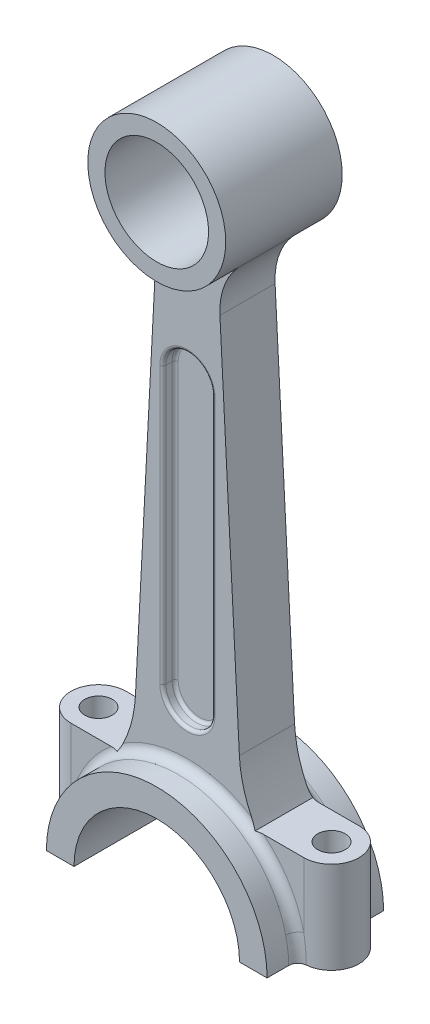
SolidWorks part; units mm, degrees
ref_plane "Front Plane" through (0, 0, 0) normal (0, 0, 1) x (1, 0, 0)
ref_plane "Top Plane" through (0, 0, 0) normal (0, 1, 0) x (1, 0, 0)
ref_plane "Right Plane" through (0, 0, 0) normal (1, 0, 0) x (0, 0, -1)
sketch "Sketch2" plane through (0, 0, 0) normal (0, 0, 1) x (1, 0, 0)
  line L0 (0, 0) -> (0, -201.2) construction
  line L1 (-10, -20.1556) -> (-17.8497, -169.9368)
  line L2 (10, -20.1556) -> (17.8497, -169.9368)
  line L3 (-36, -201.2) -> (-27, -201.2)
  line L4 (27, -201.2) -> (36, -201.2)
  circle A0 centre (0, 0) radius 16.9
  circle A1 centre (0, 0) radius 22.5
  arc A2 (27, -201.2) -> (-27, -201.2) centre (0, -201.2) ccw
  arc A3 (36, -201.2) -> (-36, -201.2) centre (0, -201.2) ccw
  dimension "D1" = 45
  dimension "D2" = 33.8
  dimension "D3" = 72
  dimension "D4" = 54
  dimension "D5" = 201.2
  dimension "D6" = 20
  dimension "D7" = 6
extrude "Boss-Extrude2" add sketch "Sketch2" along normal mid plane 38 contours A0 A1 | A3 A2 | L4 A3 L3 A2 region at (-11.5231, 18.5805, 0) region at (0, -166.005, 0)
extrude "Boss-Extrude3" add sketch "Sketch2<5>" along normal mid plane 18 contours L0 A1 L1 A3 | A1 L0 A3 L2 region at (7.1843, -100.8455, 0) region at (-7.1843, -100.8455, 0)
sketch "Sketch2<5>" plane through (0, 0, 0) normal (0, 0, 1) x (1, 0, 0) same geometry as "Sketch2"
sketch "Sketch4" plane through (0, 0, 9) normal (0, 0, 1) x (1, 0, 0)
  line L0 (0, -201.2) -> (0, 0) construction
sketch "Sketch5" plane through (0, 0, 9) normal (0, 0, 1) x (1, 0, 0)
  line L0 (0, -145.6) -> (0, -55.6) construction
  line L1 (0, -201.2) -> (0, 0) construction
  line L2 (-8, -145.6) -> (-8, -55.6)
  line L3 (8, -145.6) -> (8, -55.6)
  arc A0 (-8, -145.6) -> (8, -145.6) centre (0, -145.6) ccw
  arc A1 (8, -55.6) -> (-8, -55.6) centre (0, -55.6) ccw
  point P4 (0, -100.6)
  dimension "D2" = 8
  dimension "D1" = 90
extrude "Cut-Extrude1" cut sketch "Sketch5" against normal blind 4
mirror "Mirror1" about plane through (0, 0, 0) normal (0, 0, 1) of "Cut-Extrude1"
fillet "Fillet1" radius 1 16 edges at (0, -47.6, -5) (8, -100.6, -5) (0, -153.6, -5) (0, -47.6, -9) (8, -100.6, -9) (0, -153.6, -9) (0, -47.6, 9) (8, -100.6, 9) (0, -153.6, 9) (-8, -100.6, -5) (-8, -100.6, -9) (0, -47.6, 5) (8, -100.6, 5) (0, -153.6, 5) (-8, -100.6, 5) (-8, -100.6, 9)
fillet "Fillet2" radius 40 2 edges at (-17.8497, -169.9368, 0) (17.8497, -169.9368, 0)
fillet "Fillet3" radius 22.5 2 edges at (10, -20.1556, 0) (-10, -20.1556, 0)
ref_plane "Plane1" through (0, -171.2, 0) normal (0, -1, 0) x (-1, 0, 0)
sketch "Sketch6" plane through (0, -171.2, 0) normal (0, -1, 0) x (-1, 0, 0)
  line L0 (38, 0) -> (-38, 0) construction
  line L1 (38, -9) -> (-38, -9)
  line L2 (38, 9) -> (-38, 9)
  arc A0 (38, -9) -> (38, 9) centre (38, 0) ccw
  arc A1 (-38, 9) -> (-38, -9) centre (-38, 0) ccw
  point P2 (0, 0)
  dimension "D2" = 9
  dimension "D1" = 76
extrude "Boss-Extrude5" add sketch "Sketch6" along normal up to surface (30 mm away) up to face at (31.5, -201.2, 0)
sketch "Sketch8" plane through (0, 0, -9) normal (0, 0, -1) x (-1, 0, 0)
  line L1 (-27, -201.2) -> (27, -201.2)
  line L2 (-27, -201.2) -> (27, -201.2)
  arc A1 (27, -201.2) -> (-27, -201.2) centre (0, -201.2) ccw
  arc A2 (27, -201.2) -> (-27, -201.2) centre (0, -201.2) ccw
  dimension "D1" = 0
extrude "Cut-Extrude2" cut sketch "Sketch8" against normal through all
sketch "Sketch9" plane through (0, -171.2, 0) normal (0, 1, 0) x (1, 0, 0)
  circle A0 centre (-38, 0) radius 4.5
  circle A1 centre (38, 0) radius 4.5
  dimension "D1" = 9
  dimension "D2" = 9
extrude "Cut-Extrude3" cut sketch "Sketch9" against normal through all
fillet "Fillet4" radius 3 2 edges at (0, -165.2, -9) (0, -165.2, 9)
